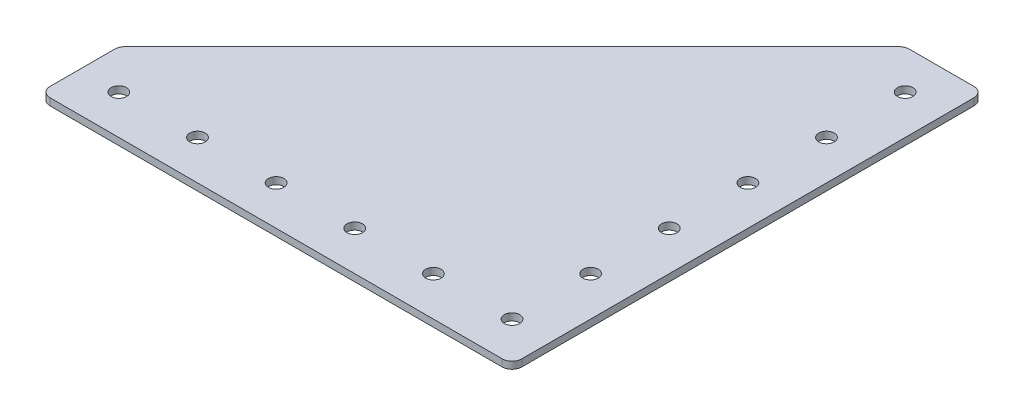
SolidWorks part; units mm, degrees
ref_plane "Front Plane" through (0, 0, 0) normal (0, 0, 1) x (1, 0, 0)
ref_plane "Top Plane" through (0, 0, 0) normal (0, 1, 0) x (1, 0, 0)
ref_plane "Right Plane" through (0, 0, 0) normal (1, 0, 0) x (0, 0, -1)
sketch "Sketch1" plane through (0, 0, 0) normal (0, 1, 0) x (1, 0, 0)
  line L0 (0, 0) -> (0, 152.4)
  line L1 (0, 152.4) -> (-25.4, 152.4)
  line L2 (-25.4, 152.4) -> (-152.4, 25.4)
  line L3 (-152.4, 25.4) -> (-152.4, 0)
  line L4 (-152.4, 0) -> (0, 0)
  circle A0 centre (-12.7, 12.7) radius 2.4892
  circle A1 centre (-38.1, 12.7) radius 2.4892
  circle A2 centre (-63.5, 12.7) radius 2.4892
  circle A3 centre (-88.9, 12.7) radius 2.4892
  circle A4 centre (-114.3, 12.7) radius 2.4892
  circle A5 centre (-12.7, 38.1) radius 2.4892
  circle A6 centre (-12.7, 63.5) radius 2.4892
  circle A7 centre (-12.7, 88.9) radius 2.4892
  circle A8 centre (-12.7, 114.3) radius 2.4892
  circle A9 centre (-139.7, 12.7) radius 2.4892
  circle A13 centre (-12.7, 139.7) radius 2.4892
  dimension "D4" = 12.7
  dimension "D5" = 12.7
  dimension "D1" = 152.4
  dimension "D2" = 25.4
  dimension "D3" = 152.4
  dimension "D10" = 25.4
  dimension "D6" = 6
  dimension "D7" = 6
extrude "Boss-Extrude2" add sketch "Sketch1" along normal mid plane 2.286
fillet "Fillet1" radius 3.175 2 edges at (0, 0, 0) (-152.4, 0, 0)
fillet "Fillet2" radius 3.175 3 edges at (-152.4, 0, -25.4) (0, 0, -152.4) (-25.4, 0, -152.4)
